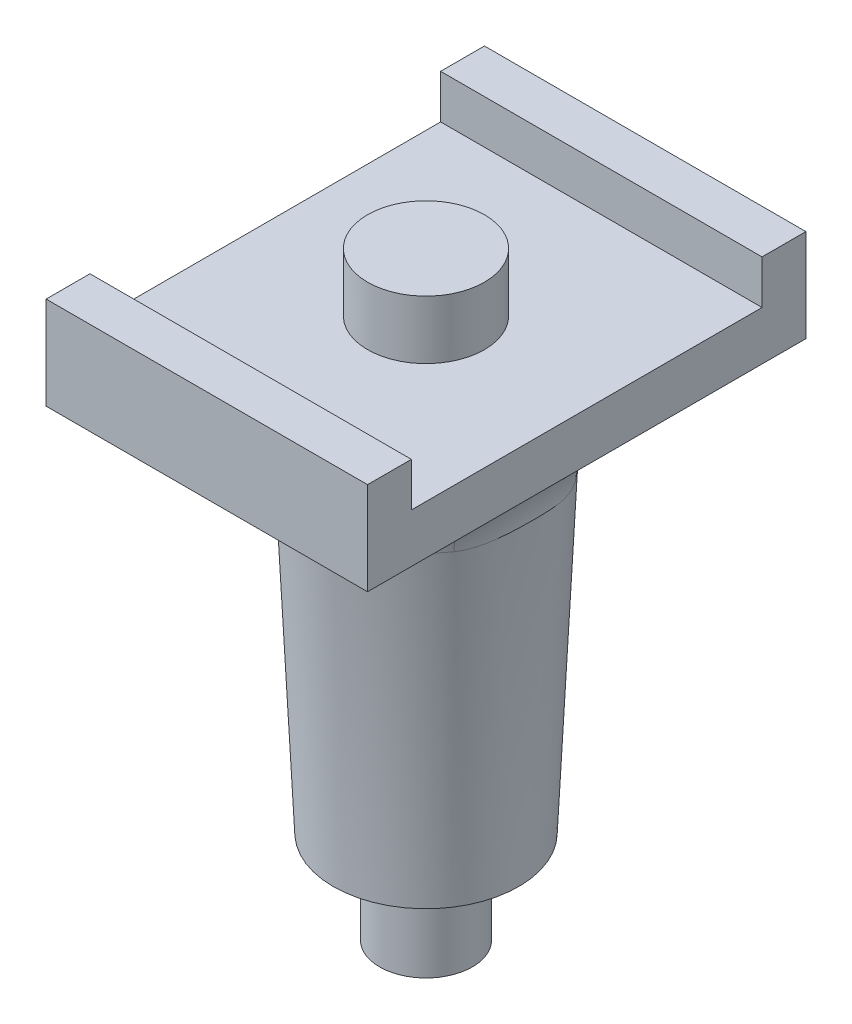
SolidWorks part; units mm, degrees
material "Plain Carbon Steel"
ref_plane "Front" through (0, 0, 0) normal (0, 0, 1) x (1, 0, 0)
ref_plane "Top" through (0, 0, 0) normal (0, 1, 0) x (1, 0, 0)
ref_plane "Right" through (0, 0, 0) normal (1, 0, 0) x (0, 0, -1)
sketch "Sketch1" plane through (0, 0, 0) normal (0, 0, 1) x (1, 0, 0)
  line L1 (11, 20) -> (-11, 20)
  line L2 (11, 20) -> (11, -20)
  line L3 (11, -20) -> (-11, -20)
  line L4 (-11, 20) -> (-11, -20)
  line L5 (11, 20) -> (-11, -20) construction
  line L6 (11, -20) -> (-11, 20) construction
  point P0 (0, 0)
  dimension "D1" = 22
  dimension "D2" = 40
extrude "Boss-Extrude1" add sketch "Sketch1" along normal mid plane 30
sketch "Sketch3" plane through (11, 0, 0) normal (1, 0, 0) x (0, 0, -1)
  line L0 (-15, 20) -> (15, 20) construction
  line L1 (-12, 20) -> (12, 20)
  line L2 (-12, 20) -> (-12, 17)
  line L3 (-12, 17) -> (12, 17)
  line L4 (12, 20) -> (12, 17)
  line L5 (0, 50) -> (0, -50) construction
  dimension "D1" = 3
  dimension "D2" = 24
  dimension "D3" = 12
extrude "Cut-Extrude1" cut sketch "Sketch3" against normal blind 508
sketch "Sketch2" plane through (0, 17, 0) normal (0, 1, 0) x (1, 0, 0)
  circle A0 centre (0, 0) radius 4
  dimension "D1" = 8
extrude "Boss-Extrude2" add sketch "Sketch2" along normal blind 4
sketch "Sketch4" plane through (0, 0, 0) normal (0, 0, 1) x (1, 0, 0)
  line L1 (-11, -20) -> (11, -20) construction
  line L3 (0, -50) -> (0, 50) construction
  line L6 (0, 31.557) -> (0, -34.6504) construction
  line L7 (3.175, -20) -> (48.175, -20)
  line L8 (7.825, 13.65) -> (48.175, 13.65)
  line L9 (48.175, 13.65) -> (48.175, -20)
  line L10 (3.175, -20) -> (3.175, -13.65)
  line L11 (3.175, -13.65) -> (6.35, -13.65)
  line L12 (11, 20) -> (-11, 20) construction
  line L13 (11, -20) -> (11, 20) construction
  arc A2 (7.825, 13.65) -> (6.35, -13.65) centre (336.324, -17.7884) ccw
  dimension "D3" = 6.35
  dimension "D6" = 330
  dimension "D1" = 6.35
  dimension "D2" = 3.175
  dimension "D4" = 3.175
  dimension "D5" = 3.175
  dimension "D7" = 45
revolve "Cut-Revolve3" cut sketch "Sketch4" angle 360 about L6
fillet "Fillet1" radius 6 1 edges at (0, 13.65, 7.825)
